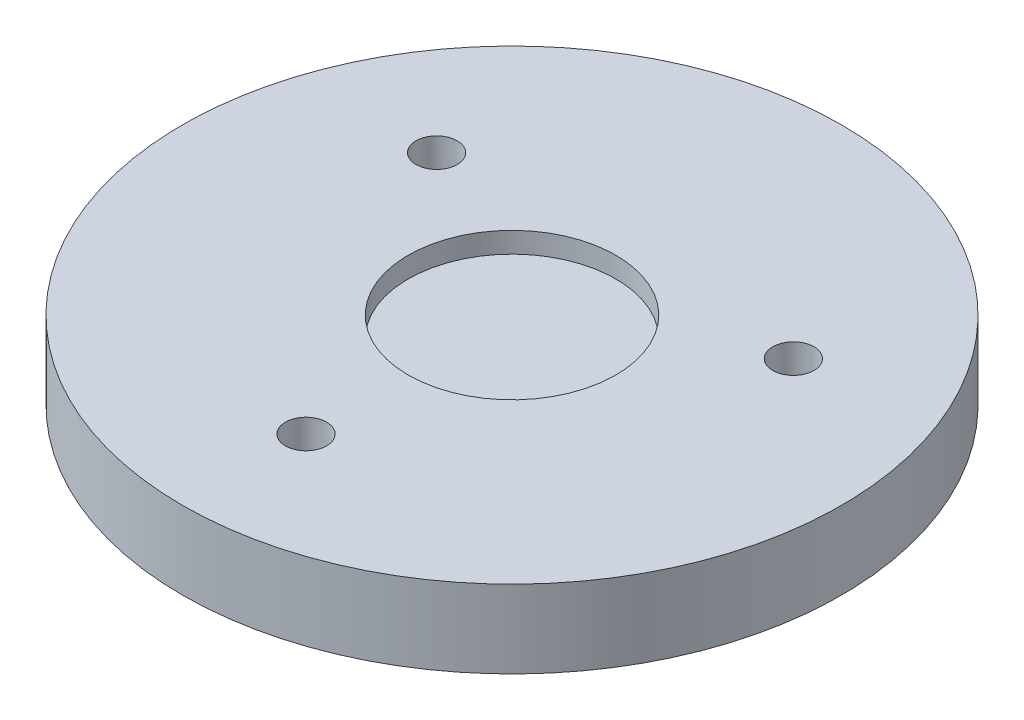
SolidWorks part; units mm, degrees
material "Beech"
ref_plane "Front Plane" through (0, 0, 0) normal (0, 0, 1) x (1, 0, 0)
ref_plane "Top Plane" through (0, 0, 0) normal (0, 1, 0) x (1, 0, 0)
ref_plane "Right Plane" through (0, 0, 0) normal (1, 0, 0) x (0, 0, -1)
sketch "Sketch1" plane through (0, 0, 0) normal (0, 1, 0) x (1, 0, 0)
  line L1 (-50.8, 50.8) -> (50.8, 50.8) construction
  line L2 (-50.8, 50.8) -> (-50.8, -50.8) construction
  line L3 (-50.8, -50.8) -> (50.8, -50.8) construction
  line L4 (50.8, 50.8) -> (50.8, -50.8) construction
  line L5 (-50.8, 50.8) -> (50.8, -50.8) construction
  line L6 (-50.8, -50.8) -> (50.8, 50.8) construction
  circle A0 centre (0, 0) radius 50.8
  point P0 (0, 0)
  dimension "D1" = 101.6
extrude "Boss-Extrude1" add sketch "Sketch1" along normal blind 11.9888
sketch "Coupling Circle" plane through (0, 0, 0) normal (0, -1, 0) x (1, 0, 0)
  circle A0 centre (0, 0) radius 31.75
  dimension "D1" = 63.5
sketch "Sketch3" plane through (0, 0, 0) normal (0, -1, 0) x (1, 0, 0)
  line L0 (0, 31.75) -> (0, 0) construction
  circle A0 centre (0, 31.75) radius 3.175
  circle A1 centre (0, 0) radius 31.75 construction
  dimension "D1" = 6.35
extrude "Cut-Extrude1" cut sketch "Sketch3" against normal through all
ref_axis "Axis1" through (0, 0, 0) along (0, -1, 0)
pattern_circular "CirPattern1" count 3 over 360 about axis through (0, 0, 0) along (0, -1, 0) of "Cut-Extrude1"
sketch "Sketch4" plane through (0, 11.9888, 0) normal (0, 1, 0) x (1, 0, 0)
  circle A0 centre (0, 0) radius 16.002
  dimension "D1" = 32.004
extrude "Cut-Extrude2" cut sketch "Sketch4" against normal blind 3.175
equation "\"coupling_diam\"= 2.5"
equation "\"plate_diam\"= 4"
equation "\"dowel_diam\"= 0.25"
equation "\"ball_diam\" = 0.375"
equation "\"D1@Sketch1\"=\"plate_diam\""
